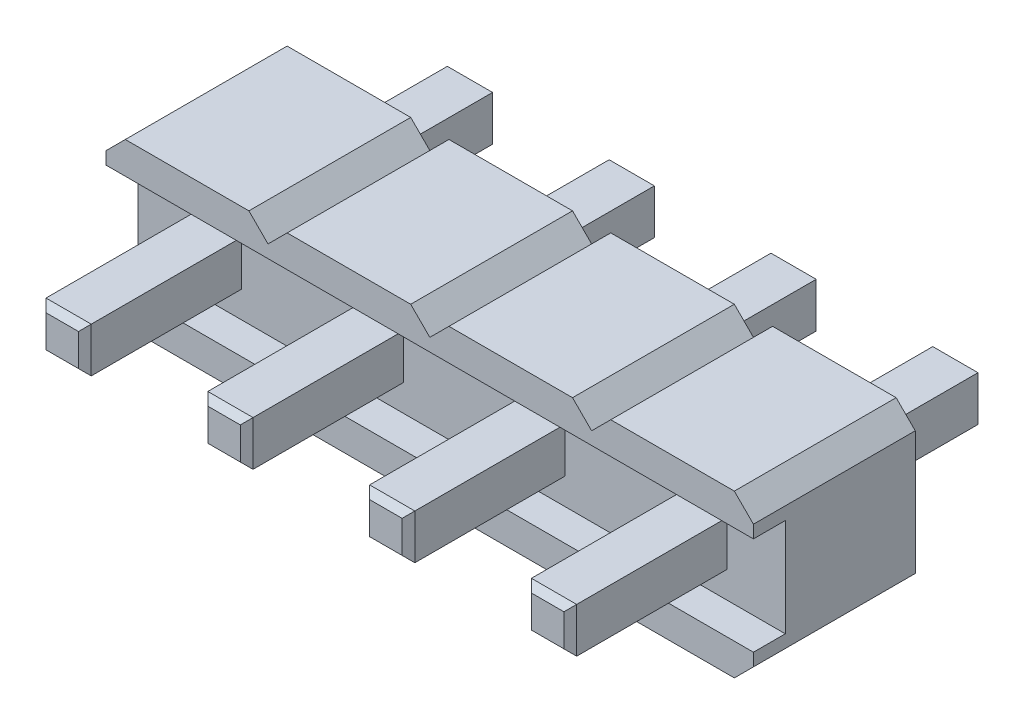
SolidWorks part; units mm, degrees
ref_plane "前视基准面" through (0, 0, 0) normal (0, 0, 1) x (1, 0, 0)
ref_plane "上视基准面" through (0, 0, 0) normal (0, 1, 0) x (1, 0, 0)
ref_plane "右视基准面" through (0, 0, 0) normal (1, 0, 0) x (0, 0, -1)
sketch "草图1" plane through (0, 0, 0) normal (0, 0, 1) x (1, 0, 0)
  line L0 (2.185, 0.3521) -> (2.895, 0.3521)
  line L1 (-0.355, 0.3521) -> (0.355, 0.3521)
  line L2 (-0.355, 0.3521) -> (-0.355, -0.3521)
  line L3 (-0.355, -0.3521) -> (0.355, -0.3521)
  line L4 (0.355, 0.3521) -> (0.355, -0.3521)
  line L5 (-0.355, 0.3521) -> (0.355, -0.3521) construction
  line L6 (-0.355, -0.3521) -> (0.355, 0.3521) construction
  line L7 (2.185, 0.3521) -> (2.185, -0.3521)
  line L8 (2.185, -0.3521) -> (2.895, -0.3521)
  line L9 (2.895, 0.3521) -> (2.895, -0.3521)
  line L10 (2.185, 0.3521) -> (2.895, -0.3521) construction
  line L11 (2.185, -0.3521) -> (2.895, 0.3521) construction
  line L12 (4.725, 0.3521) -> (5.435, 0.3521)
  line L13 (4.725, 0.3521) -> (4.725, -0.3521)
  line L14 (4.725, -0.3521) -> (5.435, -0.3521)
  line L15 (5.435, 0.3521) -> (5.435, -0.3521)
  line L16 (4.725, 0.3521) -> (5.435, -0.3521) construction
  line L17 (4.725, -0.3521) -> (5.435, 0.3521) construction
  line L18 (7.265, 0.3521) -> (7.975, 0.3521)
  line L19 (7.265, 0.3521) -> (7.265, -0.3521)
  line L20 (7.265, -0.3521) -> (7.975, -0.3521)
  line L21 (7.975, 0.3521) -> (7.975, -0.3521)
  line L22 (7.265, 0.3521) -> (7.975, -0.3521) construction
  line L23 (7.265, -0.3521) -> (7.975, 0.3521) construction
  circle A0 centre (0, 0) radius 0.5 construction
  circle A1 centre (2.54, 0) radius 0.5 construction
  circle A2 centre (5.08, 0) radius 0.5 construction
  circle A3 centre (7.62, 0) radius 0.5 construction
  dimension "D1" = 4
extrude "凸台-拉伸1" add sketch "草图1" along normal blind 10
sketch "草图2" plane through (0, 0, 0) normal (0, 0, 1) x (1, 0, 0)
  line L1 (-1.27, 1.27) -> (1.27, 1.27)
  line L2 (-1.27, 1.27) -> (-1.27, -1.27)
  line L3 (-1.27, -1.27) -> (1.27, -1.27)
  line L5 (-1.27, 1.27) -> (1.27, -1.27) construction
  line L6 (-1.27, -1.27) -> (1.27, 1.27) construction
  line L7 (6.35, 1.27) -> (8.89, 1.27)
  line L9 (6.35, -1.27) -> (8.89, -1.27)
  line L10 (8.89, 1.27) -> (8.89, -1.27)
  line L11 (6.35, 1.27) -> (8.89, -1.27) construction
  line L12 (6.35, -1.27) -> (8.89, 1.27) construction
  line L13 (1.27, 1.27) -> (6.35, 1.27)
  line L14 (6.35, -1.27) -> (1.27, -1.27)
  point P0 (0, 0)
  point P6 (7.62, 0)
extrude "凸台-拉伸2" add sketch "草图2" along normal blind 2.54
sketch "草图4" plane through (0, 0, 2.54) normal (0, 0, 1) x (1, 0, 0)
  line L0 (-1.27, 1.27) -> (-1.27, -1.27) construction
  line L1 (-1.27, 0.77) -> (8.89, 0.77)
  line L2 (-1.27, 0.77) -> (-1.27, -0.77)
  line L3 (-1.27, -0.77) -> (8.89, -0.77)
  line L4 (8.89, 0.77) -> (8.89, -0.77)
  line L5 (8.89, -1.27) -> (8.89, 1.27) construction
  line L6 (8.89, 1.27) -> (-1.27, 1.27) construction
  line L7 (-1.27, -1.27) -> (8.89, -1.27) construction
  dimension "D1" = 0.5
  dimension "D2" = 0.5
extrude "切除-拉伸2" cut sketch "草图4" against normal blind 0.5
extrude "凸台-拉伸3" add sketch "草图1<2>" against normal blind 2
sketch "草图1<2>" plane through (0, 0, 0) normal (0, 0, 1) x (1, 0, 0) same geometry as "草图1"
sketch "草图3" plane through (0, 0, 0) normal (0, 0, -1) x (-1, 0, 0)
  line L0 (-8.89, 1.27) -> (-6.35, 1.27) construction
  line L1 (-8.89, 1.27) -> (1.27, 1.27) construction
  line L2 (-6.35, 1.27) -> (-6.35, -1.27) construction
  line L3 (1.27, -1.27) -> (-8.89, -1.27) construction
  line L4 (-6.35, -1.27) -> (-3.81, -1.27) construction
  line L5 (-3.81, -1.27) -> (-3.81, 1.27) construction
  line L6 (-3.81, 1.27) -> (-1.27, 1.27) construction
  line L7 (-1.27, 1.27) -> (-1.27, -1.27) construction
  line L8 (-8.59, 1.27) -> (-8.89, 0.97)
  line L9 (-8.89, -1.27) -> (-8.89, 1.27) construction
  line L10 (-6.05, 1.27) -> (-6.35, 0.97)
  line L11 (-6.65, 1.27) -> (-6.35, 0.97)
  line L12 (-8.59, 1.27) -> (-8.89, 1.27)
  line L13 (-8.89, 1.27) -> (-8.89, 0.97)
  line L14 (-6.65, 1.27) -> (-6.05, 1.27)
  line L15 (-3.51, 1.27) -> (-3.81, 0.97)
  line L16 (-4.11, 1.27) -> (-3.81, 0.97)
  line L17 (-4.11, 1.27) -> (-3.51, 1.27)
  line L18 (-0.97, 1.27) -> (-1.27, 0.97)
  line L19 (-1.57, 1.27) -> (-1.27, 0.97)
  line L20 (-1.57, 1.27) -> (-0.97, 1.27)
  line L21 (1.57, 1.27) -> (1.27, 0.97)
  line L22 (0.97, 1.27) -> (1.27, 0.97)
  line L23 (0.97, 1.27) -> (1.57, 1.27)
  line L24 (-8.89, 0) -> (1.27, 0) construction
  line L25 (1.27, 1.27) -> (1.27, -1.27) construction
  line L26 (-3.81, -1.27) -> (-1.27, -1.27) construction
  line L27 (-8.89, -1.27) -> (-6.35, -1.27) construction
  line L28 (0.97, -1.27) -> (1.57, -1.27)
  line L29 (0.97, -1.27) -> (1.27, -0.97)
  line L30 (1.57, -1.27) -> (1.27, -0.97)
  line L31 (-1.57, -1.27) -> (-0.97, -1.27)
  line L32 (-1.57, -1.27) -> (-1.27, -0.97)
  line L33 (-0.97, -1.27) -> (-1.27, -0.97)
  line L34 (-4.11, -1.27) -> (-3.51, -1.27)
  line L35 (-4.11, -1.27) -> (-3.81, -0.97)
  line L36 (-3.51, -1.27) -> (-3.81, -0.97)
  line L37 (-6.65, -1.27) -> (-6.05, -1.27)
  line L38 (-8.89, -1.27) -> (-8.89, -0.97)
  line L39 (-8.59, -1.27) -> (-8.89, -1.27)
  line L40 (-6.65, -1.27) -> (-6.35, -0.97)
  line L41 (-6.05, -1.27) -> (-6.35, -0.97)
  line L42 (-8.59, -1.27) -> (-8.89, -0.97)
  dimension "D1" = 0.3
  dimension "D2" = 0.3
  dimension "D3" = 2
  dimension "D4" = 4
extrude "切除-拉伸1" cut sketch "草图3" against normal blind 2.54
extrude "凸台-拉伸4" add sketch "草图1<3>" along normal blind 4.5
sketch "草图1<3>" plane through (0, 0, 0) normal (0, 0, 1) x (1, 0, 0) same geometry as "草图1"
chamfer "倒角1" distance 0.1 angle 45 32 edges at (7.62, -0.3521, 4.5) (7.265, 0, 4.5) (7.62, 0.3521, 4.5) (7.975, 0, 4.5) (5.08, -0.3521, 4.5) (4.725, 0, 4.5) (5.08, 0.3521, 4.5) (5.435, 0, 4.5) (2.54, -0.3521, 4.5) (2.185, 0, 4.5) (2.54, 0.3521, 4.5) (2.895, 0, 4.5) (0, -0.3521, 4.5) (-0.355, 0, 4.5) (0, 0.3521, 4.5) (0.355, 0, 4.5) (7.62, 0.3521, -2) (7.265, 0, -2) (7.62, -0.3521, -2) (7.975, 0, -2) (5.08, 0.3521, -2) (4.725, 0, -2) (5.08, -0.3521, -2) (5.435, 0, -2) (2.54, 0.3521, -2) (2.185, 0, -2) (2.54, -0.3521, -2) (2.895, 0, -2) (0, 0.3521, -2) (-0.355, 0, -2) (0, -0.3521, -2) (0.355, 0, -2)
